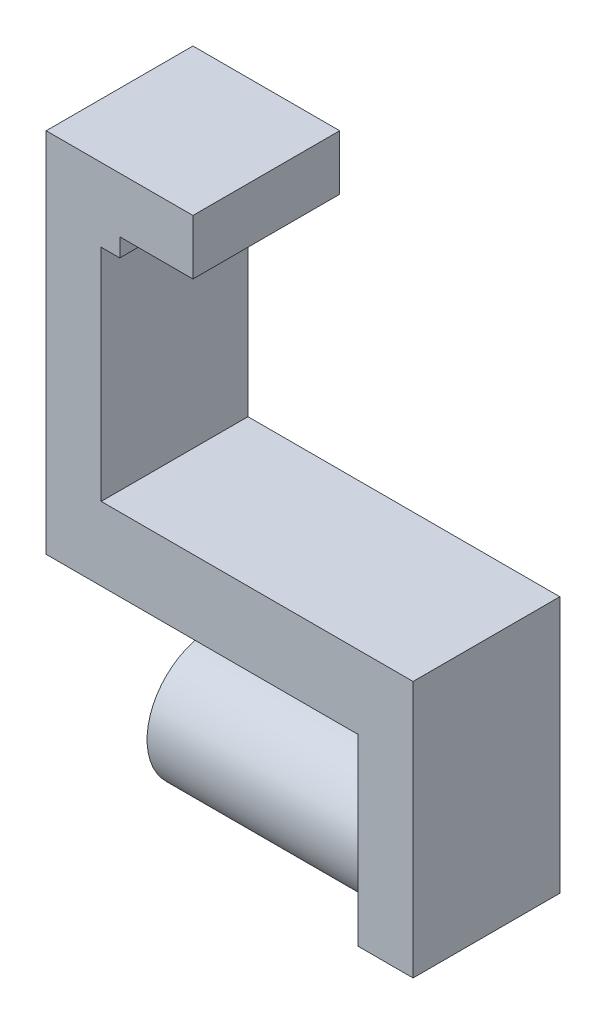
SolidWorks part; units mm, degrees
material "ASTM A36 Steel"
ref_plane "Front Plane" through (0, 0, 0) normal (0, 0, 1) x (1, 0, 0)
ref_plane "Top Plane" through (0, 0, 0) normal (0, 1, 0) x (1, 0, 0)
ref_plane "Right Plane" through (0, 0, 0) normal (1, 0, 0) x (0, 0, -1)
sketch "Sketch1" plane through (0, 0, 0) normal (1, 0, 0) x (0, 0, -1)
  circle A0 centre (0, 0) radius 11.1125
  dimension "D1" = 22.225
extrude "Boss-Extrude1" add sketch "Sketch1" against normal blind 38.1
sketch "Sketch2" plane through (0, 0, 0) normal (0, 0, 1) x (1, 0, 0)
  line L1 (0, -11.1125) -> (9.525, -11.1125)
  line L2 (0, -11.1125) -> (0, 20.6375)
  line L3 (0, 20.6375) -> (9.525, 20.6375)
  line L4 (9.525, -11.1125) -> (9.525, 20.6375)
  dimension "D1" = 9.525
  dimension "D2" = 31.75
  dimension "D3" = 11.1125
extrude "Boss-Extrude2" add sketch "Sketch2" along normal blind 12.7 and the other way blind 12.7
sketch "Sketch3" plane through (0, 0, 0) normal (0, 0, 1) x (1, 0, 0)
  line L1 (-53.975, 20.6375) -> (9.525, 20.6375)
  line L2 (-53.975, 20.6375) -> (-53.975, 33.3375)
  line L3 (-53.975, 33.3375) -> (9.525, 33.3375)
  line L4 (9.525, 20.6375) -> (9.525, 33.3375)
  dimension "D1" = 63.5
  dimension "D2" = 12.7
  dimension "D3" = 20.6375
  dimension "D4" = 53.975
extrude "Boss-Extrude3" add sketch "Sketch3" along normal blind 12.7 and the other way blind 12.7
sketch "Sketch4" plane through (0, 0, 0) normal (0, 0, 1) x (1, 0, 0)
  line L1 (-53.975, 20.6375) -> (-44.45, 20.6375)
  line L2 (-53.975, 20.6375) -> (-53.975, 84.1375)
  line L3 (-53.975, 84.1375) -> (-44.45, 84.1375)
  line L4 (-44.45, 20.6375) -> (-44.45, 84.1375)
  dimension "D1" = 9.525
  dimension "D3" = 20.6375
  dimension "D4" = 53.975
  dimension "D2" = 63.5
extrude "Boss-Extrude4" add sketch "Sketch4" along normal blind 12.7 and the other way blind 12.7
sketch "Sketch5" plane through (0, 0, 0) normal (0, 0, 1) x (1, 0, 0)
  line L5 (-53.975, 71.4375) -> (-41.2394, 71.4375)
  line L6 (-53.975, 84.1375) -> (-53.975, 20.6375) construction
  line L7 (-41.2394, 71.4375) -> (-41.2394, 74.6125)
  line L8 (-41.2394, 74.6125) -> (-28.575, 74.6125)
  line L9 (-28.575, 74.6125) -> (-28.575, 84.1375)
  line L10 (-28.575, 84.1375) -> (-53.975, 84.1375)
  line L11 (-53.975, 84.1375) -> (-53.975, 71.4375)
  dimension "D1" = 12.7
  dimension "D2" = 3.175
  dimension "D3" = 12.6644
  dimension "D4" = 25.4
  dimension "D5" = 84.1375
  dimension "D6" = 53.975
extrude "Boss-Extrude5" add sketch "Sketch5" along normal blind 12.7 and the other way blind 12.7
equation "\"F\"= 700"
equation "\"SF\"= 4"
equation "\"Sy\"= 36000"
equation "\"E\"= 29000000"
equation "\"dmax\"= 0.005"
equation "\"LA\"= 1.5"
equation "\"LB\"= 1.25"
equation "\"LC\"= 2.5"
equation "\"LD\"= 1.5"
equation "\"LE\"= 1"
equation "\"W\"= 1"
equation "\"tprac\"= 0.375"
equation "\"step\"= 0.125"
equation "\"slotW\"= 0.4986"
equation "\"slotD\"= 0.125"
equation "\"P\"= \"F\" / 2"
equation "\"sigA\"= \"Sy\" / \"SF\""
equation "\"MA\"= \"P\" * \"LA\""
equation "\"dAmin\"= ( 32 * \"MA\" / ( pi * \"sigA\" ) ) ^ ( 1 / 3 )"
equation "\"dA\"= ( int( \"dAmin\" / \"step\" ) + 1 ) * \"step\""
equation "\"MC\"= \"P\" * \"LC\" / 4"
equation "\"hCmin\"= sqr( 6 * \"MC\" / ( \"W\" * \"sigA\" ) )"
equation "\"hC\"= ( int( \"hCmin\" / \"step\" ) + 1 ) * \"step\""
equation "\"ME\"= ( \"P\" / 2 ) * \"LE\""
equation "\"hEmin\"= sqr( 6 * \"ME\" / ( \"W\" * \"sigA\" ) )"
equation "\"hE\"= ( int( ( \"hEmin\" + \"slotD\" ) / \"step\" ) + 1 ) * \"step\""
equation "\"tB\"= \"tprac\""
equation "\"tD\"= \"tprac\""
equation "\"yb\"= \"LB\" - \"dA\" / 2"
equation "\"hD\"= \"hC\" + \"LD\" + \"hE\""
equation "\"yD\"= \"yb\" + \"hD\""
equation "\"xl\"= \"LC\" - \"tB\""
equation "\"D1@Sketch1\" = \"dA\""
equation "\"D1@Sketch2\" = \"tB\""
equation "\"D2@Sketch2\" = \"LB\""
equation "\"D3@Sketch2\" = \"dA\" / 2"
equation "\"D1@Sketch3\" = \"LC\""
equation "\"D2@Sketch3\" = \"hC\""
equation "\"D3@Sketch3\" = \"yb\""
equation "\"D4@Sketch3\" = \"xl\""
equation "\"D1@Sketch4\" = \"tD\""
equation "\"D2@Sketch4\" = \"hD\""
equation "\"D1@Sketch5\" = \"hE\""
equation "\"D2@Sketch5\" = \"slotD\""
equation "\"D3@Sketch5\" = \"slotW\""
equation "\"D4@Sketch5\" = \"LE\""
equation "\"D5@Sketch5\"= \"yD\""
